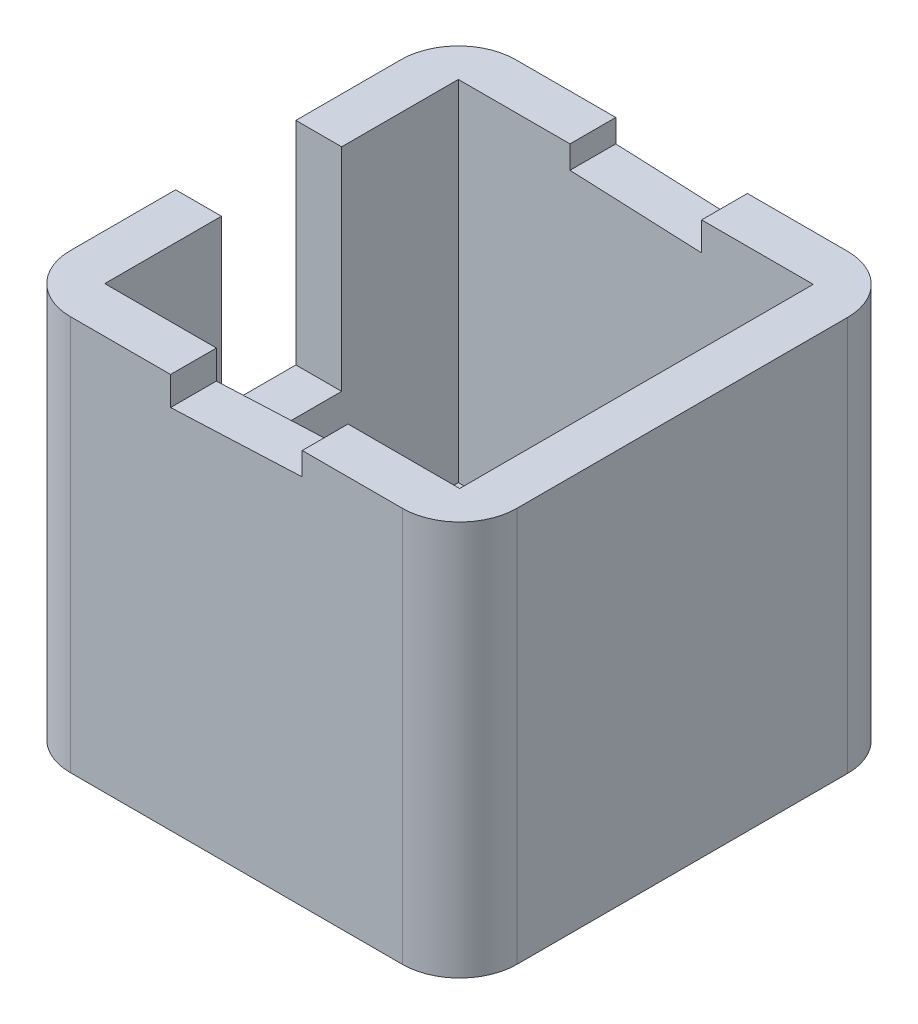
SolidWorks part; units mm, degrees
ref_plane "Front Plane" through (0, 0, 0) normal (0, 0, 1) x (1, 0, 0)
ref_plane "Top Plane" through (0, 0, 0) normal (0, 1, 0) x (1, 0, 0)
ref_plane "Right Plane" through (0, 0, 0) normal (1, 0, 0) x (0, 0, -1)
sketch "Sketch1" plane through (0, 0, 0) normal (0, 1, 0) x (1, 0, 0)
  line L1 (0, 0) -> (62, 0)
  line L2 (0, 0) -> (0, 61.7705)
  line L3 (0, 61.7705) -> (62, 61.7705)
  line L4 (62, 0) -> (62, 61.7705)
  line L9 (-8, -8) -> (70, -8)
  line L10 (-8, -8) -> (-8, 69.7705)
  line L11 (-8, 69.7705) -> (70, 69.7705)
  line L12 (70, -8) -> (70, 69.7705)
  circle A0 centre (31, 31) radius 22.5
  circle A1 centre (31, 31) radius 27.5
  circle A4 centre (5.6569, 56.1137) radius 2
  circle A5 centre (5.6569, 56.1137) radius 4
  circle A6 centre (56.3431, 56.1137) radius 2
  circle A7 centre (56.3431, 56.1137) radius 4
  circle A8 centre (56.3431, 5.6569) radius 4
  circle A9 centre (5.6569, 5.6569) radius 4
  circle A10 centre (5.6569, 5.6569) radius 2
  circle A11 centre (56.3431, 5.6569) radius 2
  dimension "D1" = 62
  dimension "D3" = 31
  dimension "D4" = 5
  dimension "D6" = 8
  dimension "D2" = 8
  dimension "D5" = 8
  dimension "D7" = 8
extrude "Boss-Extrude6" add sketch "Sketch1" along normal blind 8 contours L1 L4 L3 L2 A7 A1 A5 A8 A9 | A10 | A9 A10 | A11 | A8 A11 | A6 | A7 A6 | A4 | A5 A4 | A1 A0 | A0 region at (0.8752, 0, -30.8853) region at (31, 0, -31) region at (4.2778, 0, -31) region at (5.6569, 0, -56.1137) region at (1.77, 0, -56.1137) region at (56.3431, 0, -56.1137) region at (52.4563, 0, -56.1137) region at (52.4563, 0, -5.6569) region at (1.77, 0, -5.6569) region at (5.6569, 0, -5.6569) region at (56.3431, 0, -5.6569)
extrude "Boss-Extrude9" add sketch "Sketch1<15>" along normal blind 69 contours L3 L4 L1 L2 | L12 L11 L10 L9
sketch "Sketch1<15>" plane through (0, 0, 0) normal (0, 1, 0) x (1, 0, 0) same geometry as "Sketch1"
extrude "Cut-Extrude2" cut sketch "Sketch1<17>" along normal blind 56 contours A9 | A8 | A7 | A5
sketch "Sketch1<17>" plane through (0, 0, 0) normal (0, 1, 0) x (1, 0, 0) same geometry as "Sketch1"
extrude "Boss-Extrude10" add sketch "Sketch1<18>" along normal blind 4 contours A11 | A8 | A10 | A9 | A4 | A5 | A6 | A7
sketch "Sketch1<18>" plane through (0, 0, 0) normal (0, 1, 0) x (1, 0, 0) same geometry as "Sketch1"
ref_plane "Plane2" through (0, 0, -69.7705) normal (0, 0, -1) x (-1, 0, 0)
sketch "Sketch3" plane through (0, 0, -69.7705) normal (0, 0, -1) x (-1, 0, 0)
  line L15 (8, 69) -> (-70, 69) construction
  line L17 (-42.5, 69) -> (-42.5, 64)
  line L18 (-42.5, 64) -> (-19.5, 65)
  line L19 (-19.5, 65) -> (-19.5, 69)
  line L20 (-42.5, 69) -> (-19.5, 69)
  dimension "D1" = 5
  dimension "D2" = 4
ref_plane "Plane3" through (0, 0, 8) normal (0, 0, 1) x (1, 0, 0)
ref_plane "Plane4" through (-8, 0, 0) normal (-1, 0, 0) x (0, 0, 1)
sketch "Sketch6" plane through (-8, 0, 0) normal (-1, 0, 0) x (0, 0, 1)
  line L8 (8, 69) -> (-69.7705, 69) construction
  line L22 (-41.3853, 69) -> (-41.3853, 32)
  line L25 (-20.3853, 32) -> (-20.3853, 69)
  line L28 (-41.3853, 69) -> (-20.3853, 69)
  line L30 (-41.3853, 32) -> (-20.3853, 32)
  point P9 (-33.4083, 56)
  dimension "D1" = 21
  dimension "D2" = 37
fillet "Fillet3" radius 10 4 edges at (70, 34.5, -69.7705) (-8, 34.5, -69.7705) (-8, 34.5, 8) (70, 34.5, 8)
extrude "Cut-Extrude10" cut sketch "Sketch3" against normal blind 8
sketch "Sketch9" plane through (0, 0, 8) normal (0, 0, 1) x (1, 0, 0)
  line L1 (2, 69) -> (60, 69) construction
  line L3 (19.5, 69) -> (19.5, 64)
  line L4 (19.5, 64) -> (42.5, 65)
  line L5 (42.5, 65) -> (42.5, 69)
  line L6 (19.5, 69) -> (42.5, 69)
  dimension "D1" = 5
  dimension "D2" = 4
extrude "Cut-Extrude11" cut sketch "Sketch9" against normal blind 8
extrude "Cut-Extrude13" cut sketch "Sketch6" against normal blind 10
